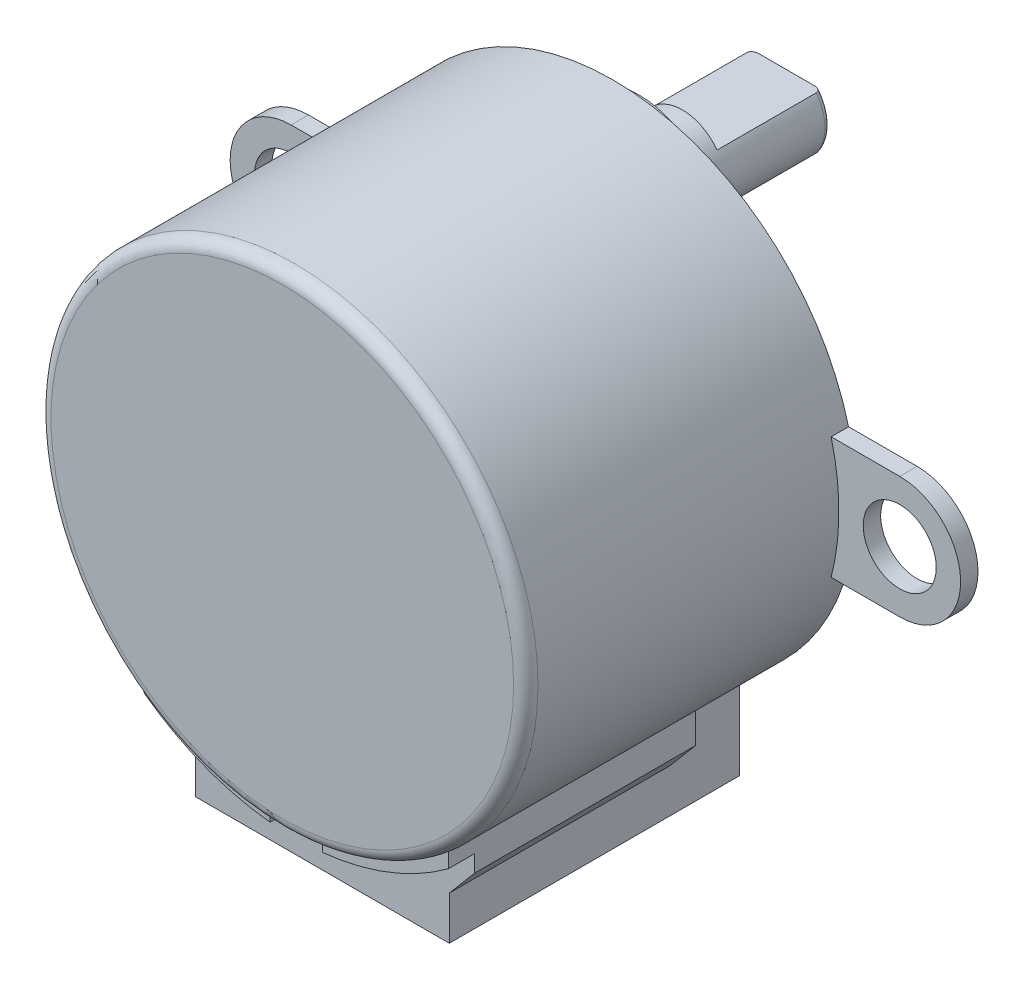
SolidWorks part; units mm, degrees
ref_plane "Ön Düzlem" through (0, 0, 0) normal (0, 0, 1) x (1, 0, 0)
ref_plane "Üst Düzlem" through (0, 0, 0) normal (0, 1, 0) x (1, 0, 0)
ref_plane "Sağ Düzlem" through (0, 0, 0) normal (1, 0, 0) x (0, 0, -1)
sketch "Sketch1" plane through (0, 0, 0) normal (0, 0, 1) x (1, 0, 0)
  circle A0 centre (0, 0) radius 14
extrude "Boss-Extrude1" add sketch "Sketch1" along normal blind 19
sketch "Sketch2" plane through (0, 0, 0) normal (0, 0, -1) x (-1, 0, 0)
  circle A0 centre (0, 8) radius 4.5
  point P0 (0, 8)
extrude "Boss-Extrude2" add sketch "Sketch2" along normal blind 1.5
sketch "Sketch3" plane through (0, 0, -1.5) normal (0, 0, -1) x (-1, 0, 0)
  circle A0 centre (0, 8) radius 2.5
extrude "Boss-Extrude3" add sketch "Sketch3" along normal blind 2.5
sketch "Sketch5" plane through (0, 0, -4) normal (0, 0, -1) x (-1, 0, 0)
  line L1 (-2, 9.5) -> (2, 9.5)
  line L3 (-2, 6.5) -> (2, 6.5)
  arc A0 (2, 6.5) -> (2, 9.5) centre (0, 8) ccw
  arc A1 (-2, 9.5) -> (-2, 6.5) centre (0, 8) ccw
extrude "Boss-Extrude5" add sketch "Sketch5" along normal blind 6
fillet "Fillet1" radius 0.3 2 edges at (-2.5, 8, -10) (2.5, 8, -10)
fillet "Fillet2" radius 0.7 1 edges at (14, 0, 19)
sketch "Sketch6" plane through (0, 0, 0) normal (0, 0, -1) x (-1, 0, 0)
  line L0 (0, 3.5) -> (0, -3.5268) construction
  line L1 (-17.5, 3.5) -> (-13.5554, 3.5)
  line L3 (17.5, -3.5) -> (13.5554, -3.5)
  line L4 (-13.5554, -3.5) -> (-17.5, -3.5)
  line L5 (13.5554, 3.5) -> (17.5, 3.5)
  arc A0 (-17.5, 3.5) -> (-17.5, -3.5) centre (-17.5, 0) ccw
  circle A1 centre (-17.5, 0) radius 2.1
  circle A2 centre (0, 8) radius 4.5 construction
  circle A3 centre (0, 8) radius 4.5 construction
  arc A4 (17.5, 3.5) -> (17.5, -3.5) centre (17.5, 0) cw
  circle A5 centre (17.5, 0) radius 2.1
  arc A6 (13.5554, -3.5) -> (13.5554, 3.5) centre (0, 0) ccw
  arc A7 (-13.5554, 3.5) -> (-13.5554, -3.5) centre (0, 0) ccw
  dimension "D1" = 7
  dimension "D2" = 17.5
extrude "Boss-Extrude6" add sketch "Sketch6" against normal blind 1
sketch "Sketch7" plane through (0, 0, 0) normal (0, 0, -1) x (-1, 0, 0)
  line L2 (-7.3, -11.9461) -> (-7.3, -17)
  line L3 (-7.3, -17) -> (7.3, -17)
  line L4 (7.3, -11.9461) -> (7.3, -17)
  arc A0 (-7.3, -11.9461) -> (7.3, -11.9461) centre (0, 0) ccw
  dimension "D1" = 17
  dimension "D2" = 14.6
extrude "Boss-Extrude7" add sketch "Sketch7" against normal blind 16.7
sketch "Sketch8" plane through (0, 0, 16.7) normal (0, 0, 1) x (1, 0, 0)
  line L0 (-7.3, -14.5) -> (-8.75, -12.785)
  line L1 (-7.3, -14.5) -> (-7.3, -11.9461)
  line L2 (-8.75, -10.9287) -> (-8.75, -12.785)
  line L4 (8.75, -10.9287) -> (8.75, -12.785)
  line L9 (8.75, -12.785) -> (7.3, -14.5)
  line L10 (7.3, -11.9461) -> (7.3, -14.5)
  arc A0 (-8.75, -10.9287) -> (-7.3, -11.9461) centre (0, 0) ccw
  arc A1 (7.3, -11.9461) -> (8.75, -10.9287) centre (0, 0) ccw
  dimension "D1" = 17.5
extrude "Boss-Extrude8" add sketch "Sketch8" against normal blind 12.7
sketch "Sketch9" plane through (0, 0, -10) normal (0, 0, -1) x (-1, 0, 0)
  circle A0 centre (0, 8) radius 0.4315
extrude "Cut-Extrude1" cut sketch "Sketch9" against normal blind 0.3
sketch "Sketch10" plane through (0, 0, 16.7) normal (0, 0, 1) x (1, 0, 0)
  line L0 (-8.75, -11.8122) -> (-8.75, -10.9287)
  line L2 (-1.5, -13.9194) -> (-1.5, -14.6233)
  line L4 (1.5, -13.9194) -> (1.5, -14.6233)
  line L7 (8.75, -10.9287) -> (8.75, -11.8122)
  arc A0 (-8.75, -11.8122) -> (-1.5, -14.6233) centre (0, 0) ccw
  arc A1 (-8.75, -10.9287) -> (-1.5, -13.9194) centre (0, 0) ccw
  arc A2 (1.5, -14.6233) -> (8.75, -11.8122) centre (0, 0) ccw
  arc A3 (1.5, -13.9194) -> (8.75, -10.9287) centre (0, 0) ccw
  dimension "D1" = 3
extrude "Boss-Extrude10" add sketch "Sketch10" along normal blind 1.5
sketch "Sketch11" plane through (0, -17, 0) normal (0, -1, 0) x (1, 0, 0)
  line L0 (7.3, 0) -> (-7.3, 0) construction
  line L1 (-3.75, 4.2) -> (3.75, 4.2)
  line L2 (-3.75, 4.2) -> (-3.75, 3)
  line L3 (-3.75, 3) -> (3.75, 3)
  line L4 (3.75, 4.2) -> (3.75, 3)
  dimension "D1" = 7.5
  dimension "D2" = 1.2
  dimension "D3" = 3.75
  dimension "D4" = 3
extrude "Cut-Extrude2" cut sketch "Sketch11" against normal blind 2
sketch "Sketch12" plane through (0, -15, 0) normal (0, -1, 0) x (1, 0, 0)
  line L0 (-3.75, 3.6) -> (3.75, 3.6) construction
  line L1 (-3.75, 4.2) -> (-3.75, 3) construction
  line L2 (3.75, 3) -> (3.75, 4.2) construction
  line L3 (0, 3.6) -> (0, 1.54) construction
  circle A0 centre (-2.4, 3.6) radius 0.5
  circle A1 centre (-1.2, 3.6) radius 0.5
  circle A2 centre (0, 3.6) radius 0.5
  circle A3 centre (1.2, 3.6) radius 0.5
  circle A4 centre (2.4, 3.6) radius 0.5
  dimension "D1" = 1.2
  dimension "D2" = 1.2
extrude "Boss-Extrude11" add sketch "Sketch12" along normal blind 32
ref_plane "Plano1" through (0, -20, 0) normal (0, 1, 0) x (1, 0, 0)
sketch "Esboço1" plane through (0, -20, 0) normal (0, 1, 0) x (1, 0, 0)
  line L1 (-3.75, -3) -> (3.75, -3)
  line L2 (-3.75, -3) -> (-3.75, -4.2)
  line L3 (-3.75, -4.2) -> (3.75, -4.2)
  line L4 (3.75, -3) -> (3.75, -4.2)
  line L5 (-3.75, -3) -> (3.75, -4.2) construction
  line L6 (-3.75, -4.2) -> (3.75, -3) construction
  point P0 (0, -3.6)
extrude "Corte-extrusão1" cut sketch "Esboço1" against normal blind 30
sketch "Esboço3" plane through (0, 0, -9.7) normal (0, 0, -1) x (-1, 0, 0)
  point P0 (0, 8)
ref_plane "Plano2" through (0, 8, 0) normal (0, 1, 0) x (1, 0, 0)
